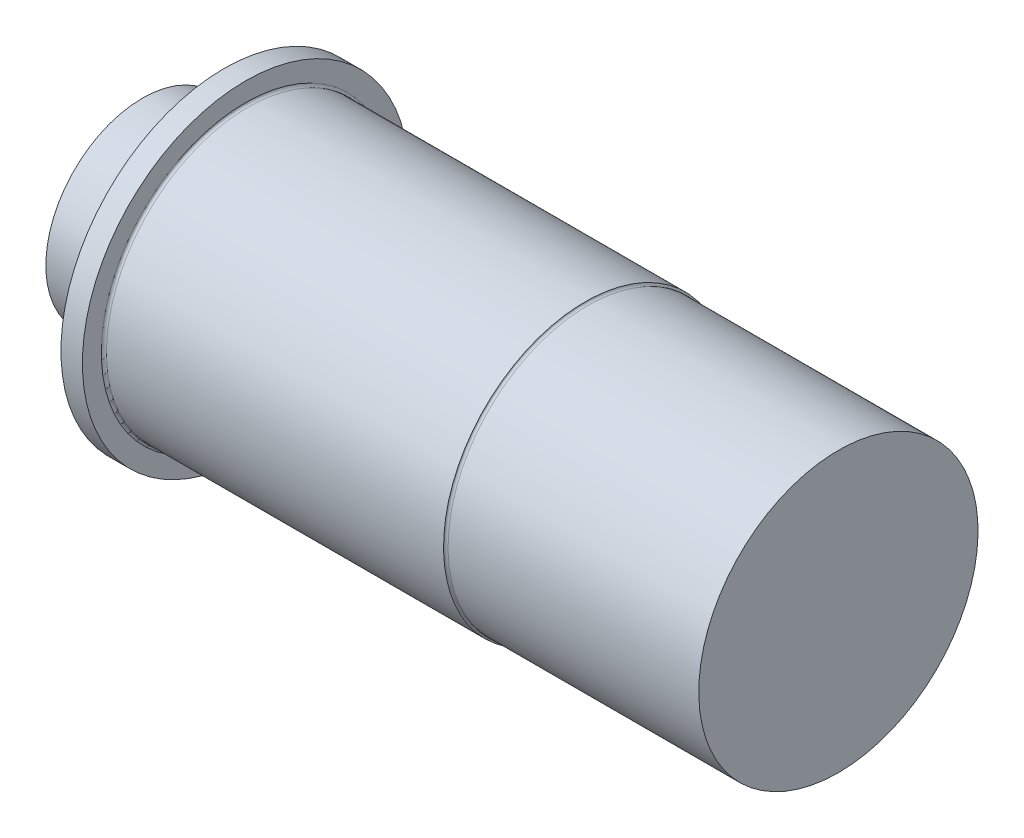
SolidWorks part; units mm, degrees
material "1.0570 (S355J2G3)"
ref_plane "Front Plane" through (0, 0, 0) normal (0, 0, 1) x (1, 0, 0)
ref_plane "Top Plane" through (0, 0, 0) normal (0, 1, 0) x (1, 0, 0)
ref_plane "Right Plane" through (0, 0, 0) normal (1, 0, 0) x (0, 0, -1)
sketch "Sketch1" plane through (0, 0, 0) normal (0, 0, 1) x (1, 0, 0)
  line L0 (-122.7657, 0) -> (122.7657, 0) construction
  line L11 (-81.0667, 0) -> (81.0667, 0)
  line L14 (-81.0667, 22.5225) -> (-62.0667, 22.5225)
  line L15 (-62.0667, 38) -> (-57.0667, 38)
  line L16 (-57.0667, 33) -> (-15.4695, 33)
  line L18 (22.0667, 32.5325) -> (40.0667, 32.5325)
  line L19 (40.0667, 32.5325) -> (81.0667, 32.5325)
  line L20 (-81.0667, 0) -> (-81.0667, 22.5225)
  line L21 (-62.0667, 22.5225) -> (-62.0667, 38)
  line L22 (-57.0667, 33) -> (-57.0667, 38)
  line L23 (81.0667, 32.5325) -> (81.0667, 0)
  line L24 (22.0667, 32.5325) -> (22.0667, 33)
  line L25 (22.0667, 33) -> (-15.4695, 33)
  point P2 (0, 0)
  point P9 (0, 0)
  point P13 (31.0667, 32.5325)
  point P15 (31.0667, 32.5325)
  dimension "D1" = 19
  dimension "D2" = 5
  dimension "D3" = 76
  dimension "D4" = 45.045
  dimension "D5" = 41.5972
  dimension "D7" = 18
  dimension "D8" = 50
  dimension "D6" = 66
  dimension "D9" = 65.065
  dimension "D10" = 37.5362
revolve "Revolve1" add sketch "Sketch1" angle 360 about L0
fillet "Fillet1" radius 0.6 3 edges at (-57.0667, -33, 0) (-62.0667, -22.5225, 0) (22.0667, -32.5325, 0)
equation "\"alpha\"= 20 'Helix angle, psi [deg]"
equation "\"beta\"= 15 'Pressure angle, theta [deg]"
equation "\"z_1\"= 18 'Number of teeth, pinion 1"
equation "\"z_2\"= 79 'Number of teeth, gear 2"
equation "\"z_3\"= 18 'Number of teeth, pinion 3"
equation "\"z_4\"= 71 'Number of teeth, gear 4"
equation "\"c_dist_1\"= 0.129 'Center distance stage 1 [m]"
equation "\"c_dist_2\"= 0.1788 'Center distance stage 2 [m]"
equation "\"m_s1\"= 2 * \"c_dist_1\" / (\"z_1\" + \"z_2\") * 1000 'Module stage 1 [mm]"
equation "\"m_s2\"= 2 * \"c_dist_2\" / (\"z_3\" + \"z_4\") * 1000 'Module stage 2 [mm]"
equation "\"d_g1\"= \"m_s1\" * \"z_1\" 'Pitch circle 1 [mm]"
equation "\"d_g2\"= \"m_s1\" * \"z_2\" 'Pitch circle 2 [mm]"
equation "\"d_g3\"= \"m_s2\" * \"z_3\" 'Pitch circle 3 [mm]"
equation "\"d_g4\"= \"m_s2\" * \"z_4\" 'Pitch circle 4 [mm]"
equation "\"ht_1\"= \"m_s1\" 'Top height 1 [mm]"
equation "\"ht_2\"= \"m_s1\" 'Top height 2 [mm]"
equation "\"ht_3\"= \"m_s2\" 'Top height 3 [mm]"
equation "\"ht_4\"= \"m_s2\" 'Top height 4 [mm]"
equation "\"hf_1\"= 1.25 * \"m_s1\" 'Bottom height 1 [mm]"
equation "\"hf_2\"= 1.25 * \"m_s1\" 'Bottom height 2 [mm]"
equation "\"hf_3\"= 1.25 * \"m_s2\" 'Bottom height 3 [mm]"
equation "\"hf_4\"= 1.25 * \"m_s2\" 'Bottom height 4 [mm]"
equation "\"dt_g1\"= \"d_g1\" + 2 * \"ht_1\" 'Addendum 1 [mm]"
equation "\"dt_g2\"= \"d_g2\" + 2 * \"ht_2\" 'Addendum 2 [mm]"
equation "\"dt_g3\"= \"d_g3\" + 2 * \"ht_3\" 'Addendum 3 [mm]"
equation "\"dt_g4\"= \"d_g4\" + 2 * \"ht_4\" 'Addendum 4 [mm]"
equation "\"df_g1\"= \"d_g1\" - 2 * \"hf_1\" 'Dedendum 1 [mm]"
equation "\"df_g2\"= \"d_g2\" - 2 * \"hf_2\" 'Dedendum 2 [mm]"
equation "\"df_g3\"= \"d_g3\" - 2 * \"hf_3\" 'Dedendum 3 [mm]"
equation "\"df_g4\"= \"d_g4\" - 2 * \"hf_4\" 'Dedendum 4 [mm]"
equation "\"p_s1\"= pi * \"m_s1\" 'Pitch 1 [mm]"
equation "\"p_s2\"= pi * \"m_s2\" 'Pitch 2 [mm]"
equation "\"sn_s1\"= \"p_s1\" / 2 - 0.05 * \"m_s1\" 'Tooth thickness 1 [mm]"
equation "\"sn_s2\"= \"p_s2\" / 2 - 0.05 * \"m_s2\" 'Tooth thickness 2 [mm]"
equation "\"en_s1\"= \"p_s1\" / 2 + 0.05 * \"m_s1\" 'Hatch width 1 [mm]"
equation "\"en_s2\"= \"p_s2\" / 2 + 0.05 * \"m_s2\" 'Hatch width 2 [mm]"
equation "\"mt_s1\"= \"m_s1\" / cos(\"beta\") 'Helical module 1"
equation "\"mt_s2\"= \"m_s2\" / cos(\"beta\") 'Helical module 2"
equation "\"lambda\"= 10 'Width factor, 8-12"
equation "\"b_s1\"= \"mt_s1\" * \"lambda\" 'Helical gear width 1"
equation "\"b_s2\"= \"mt_s2\" * \"lambda\" 'Helical gear width 2"
equation "\"pt_s1\"= \"p_s1\" / cos(\"beta\") 'Transverse pitch 1 [mm]"
equation "\"pt_s2\"= \"p_s2\" / cos(\"beta\") 'Transverse pitch 2 [mm]"
equation "\"px_s1\"= \"p_s1\" / sin(\"beta\") 'Axial pitch 1 [mm]"
equation "\"px_s2\"= \"p_s2\" / sin(\"beta\") 'Axial pitch 2 [mm]"
equation "\"dp_s1\"= pi / \"pt_s1\" 'Diametral pitch 1 [mm]"
equation "\"dp_s2\"= pi / \"pt_s2\" 'Diametral pitch 2 [mm]"
equation "\"d_S1\"= 35 'Diameter shaft 1 [mm]"
equation "\"d_C\"= 35.035 'Inner diameter bearing C [mm]"
equation "\"d_12\"= 45 'Larger diameter shaft 1 [mm]"
equation "\"d_S2_1\"= 56 'Diameter shaft 2 part 1 [mm]"
equation "\"d_S2_2\"= 56 'Diameter shaft 2 part 2 [mm]"
equation "\"d_D\"= 45.045 'Inner diameter bearing D [mm]"
equation "\"d_E\"= 45.045 'Inner diameter bearing E [mm]"
equation "\"d_45\"= 66 'Larger diameter shaft 2 [mm]"
equation "\"d_S3\"= 66 'Diameter shaft 3 [mm]"
equation "\"d_F\"= 45.045 'Inner diameter bearing F [mm]"
equation "\"d_78\"= 76 'Larger diameter shaft 3 [mm]"
equation "\"b_G1\"= \"b_s1\" 'Gear 1 width [mm]"
equation "\"b_G2\"= \"b_s1\" 'Gear 2 width [mm]"
equation "\"b_G3\"= \"b_s2\" 'Gear 3 width [mm]"
equation "\"b_G4\"= \"b_s2\" 'Gear 4 width [mm]"
equation "\"b_B\"= 13 'Bearing B width [mm]"
equation "\"b_C\"= 21 'Bearing C width [mm]"
equation "\"b_D\"= 25 'Bearing D width [mm]"
equation "\"b_E\"= 25 'Bearing E width [mm]"
equation "\"b_F\"= 19 'Bearing F width [mm]"
equation "\"b_G\"= 18 'Bearing G width [mm]"
equation "\"L_12\"= 5 '[mm]"
equation "\"L_45\"= 5 '[mm]"
equation "\"L_78\"= 5 '[mm]"
equation "\"L_AB\"= 50 '[mm]"
equation "\"L_GH\"= 50 '[mm]"
equation "\"r_S1\"= 0.5 '[mm]"
equation "\"r_S2\"= 1 '[mm]"
equation "\"r_S3\"= 0.6 '[mm] "
equation "\"D1@Sketch1\"= \"b_F\""
equation "\"D2@Sketch1\"= \"L_78\""
equation "\"D3@Sketch1\"= \"d_78\""
equation "\"D4@Sketch1\"= \"d_F\""
equation "\"D5@Sketch1\" = \"b_s2\""
equation "\"D8@Sketch1\"= \"L_GH\""
equation "\"D1@Fillet1\"=\"r_S3\""
equation "\"d_B\"= 30.03 'Inner diameter bearing B [mm]"
equation "\"d_G\"= 65.065 'Inner diameter bearing G [mm]"
equation "\"D7@Sketch1\"= \"b_G\""
equation "\"D6@Sketch1\"= \"d_S3\""
equation "\"D9@Sketch1\"= \"d_G\""
equation "\"D10@Sketch1\"= \"L_45\"+\"L_12\"+\"b_s1\""
